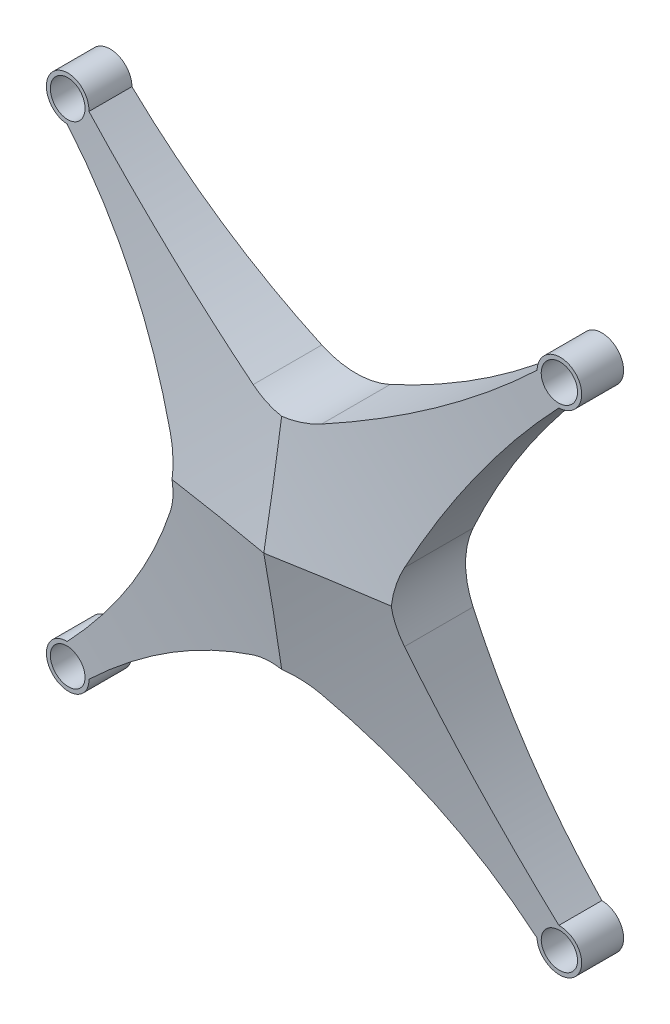
SolidWorks part; units mm, degrees
ref_plane "Front Plane" through (0, 0, 0) normal (0, 0, 1) x (1, 0, 0)
ref_plane "Top Plane" through (0, 0, 0) normal (0, 1, 0) x (1, 0, 0)
ref_plane "Right Plane" through (0, 0, 0) normal (1, 0, 0) x (0, 0, -1)
sketch "Sketch2" plane through (0, 0, 0) normal (0, 0, 1) x (1, 0, 0)
  line L0 (-63.5, 0) -> (0, 0)
  line L1 (-152.4, 152.4) -> (152.4, 152.4) construction
  line L2 (-152.4, 152.4) -> (-152.4, -152.4) construction
  line L3 (-152.4, -152.4) -> (152.4, -152.4) construction
  line L4 (152.4, 152.4) -> (152.4, -152.4) construction
  line L5 (-63.5, 63.5) -> (63.5, 63.5) construction
  line L6 (-63.5, 63.5) -> (-63.5, -63.5) construction
  line L7 (-63.5, -63.5) -> (63.5, -63.5) construction
  line L8 (63.5, 63.5) -> (63.5, -63.5) construction
  line L10 (0, 0) -> (0, -63.5)
  line L11 (-152.4, -152.4) -> (0, 0) construction
  circle A0 centre (-152.4, 152.4) radius 11 construction
  circle A1 centre (152.4, 152.4) radius 11 construction
  circle A2 centre (152.4, -152.4) radius 11 construction
  circle A3 centre (-152.4, -152.4) radius 11
  arc A4 (-152.4, -138.9) -> (-138.9, -152.4) centre (-152.4, -152.4) ccw
  arc A5 (138.9, -152.4) -> (152.4, -138.9) centre (152.4, -152.4) ccw construction
  arc A6 (152.4, 138.9) -> (138.9, 152.4) centre (152.4, 152.4) ccw construction
  arc A7 (-138.9, 152.4) -> (-152.4, 138.9) centre (-152.4, 152.4) ccw construction
  spline S0 degree 2 poles (-152.4, -138.9) (-94.5343, -78.0072) (-63.5, 0) knots 0 0 0 1 1 1
  spline S1 degree 2 poles (138.9, 152.4) (0, -25.4) (-138.9, 152.4) knots 0 0 0 1 1 1 construction
  spline S2 degree 2 poles (152.4, -138.9) (-25.4, 0) (152.4, 138.9) knots 0 0 0 1 1 1 construction
  spline S3 degree 2 poles (-138.9, -152.4) (-78.0072, -94.5343) (0, -63.5) knots 0 0 0 1 1 1
  spline S4 degree 2 poles (-63.5, 0) (-63.5, 69.45) (-152.4, 138.9) knots 0.5 0.5 0.5 1 1 1 construction
  spline S5 degree 2 poles (138.9, -152.4) (69.45, -63.5) (0, -63.5) knots 0 0 0 0.5 0.5 0.5 construction
  point P0 (0, 0)
  point P10 (0, 152.4)
  point P11 (-152.4, 0)
  point P39 (0, 0)
  point P42 (0, 0)
  dimension "D3" = 22
  dimension "D2" = 27
  dimension "D1" = 304.8
  dimension "D4" = 304.8
  dimension "D5" = 127
  dimension "D6" = 127
extrude "Boss-Extrude1" add sketch "Sketch2" along normal blind 57.15 contours A3 | L10 S3 A4 S0 L0
ref_plane "Plane2" through (0, 0, 0) normal (0.7071, -0.7071, 0) x (-0.7071, -0.7071, 0)
sketch "Sketch8" plane through (0, 0, 0) normal (0.7071, -0.7071, 0) x (-0.7071, -0.7071, 0)
  line L0 (229.2797, -25.9102) -> (229.2797, -69.0106)
  line L1 (229.2797, -69.0106) -> (0, -69.0106)
  line L2 (0, -69.0106) -> (0, -57.15)
  spline S0 degree 2 poles (229.2797, -25.9102) (112.7979, -28.2219) (0, -57.15) knots 0 0 0 1 1 1
extrude "Cut-Extrude3" cut sketch "Sketch8" against normal through all both and the other way through all contours L1 L2 S0 L0
pattern_circular "CirPattern8" count 4 over 360 about axis through (0, 0, 57.15) along (0, 0, -1) of "Cut-Extrude3", "Boss-Extrude1" reverse direction yes
fillet "Fillet2" radius 50.8 4 edges at (0, 63.5, 23.3597) (63.5, 0, 23.3597)
shell "Shell2" thickness 2.54 removed face at (0, 0, 0)
